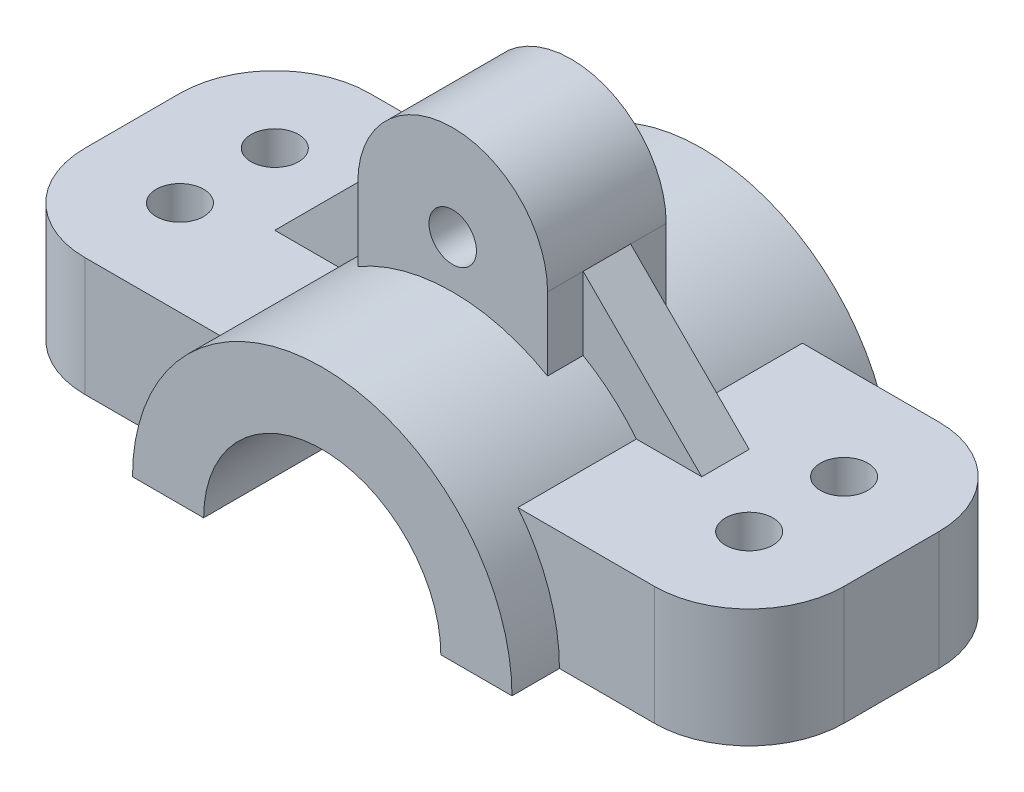
SolidWorks part; units mm, degrees
ref_plane "Front Plane" through (0, 0, 0) normal (0, 0, 1) x (1, 0, 0)
ref_plane "Top Plane" through (0, 0, 0) normal (0, 1, 0) x (1, 0, 0)
ref_plane "Right Plane" through (0, 0, 0) normal (1, 0, 0) x (0, 0, -1)
sketch "Sketch1" plane through (0, 0, 0) normal (0, 0, 1) x (1, 0, 0)
  line L0 (-40, 0) -> (-25, 0)
  line L1 (25, 0) -> (40, 0)
  arc A0 (25, 0) -> (-25, 0) centre (0, 0) ccw
  arc A1 (40, 0) -> (-40, 0) centre (0, 0) ccw
  dimension "D1" = 50
  dimension "D2" = 80
extrude "Boss-Extrude1" add sketch "Sketch1" along normal mid plane 80
sketch "Sketch2" plane through (0, 0, 0) normal (0, -1, 0) x (1, 0, 0)
  line L0 (0, 40) -> (0, 0) construction
  line L1 (25, 40) -> (-25, 40) construction
  line L2 (0, 0) -> (-88.9874, 0) construction
  line L4 (-80, 30) -> (-10, 30)
  line L5 (-80, 30) -> (-80, -30)
  line L6 (-80, -30) -> (-10, -30)
  line L7 (-10, 30) -> (-10, -30)
  dimension "D1" = 80
  dimension "D2" = 60
  dimension "D3" = 10
extrude "Boss-Extrude2" add sketch "Sketch2" against normal blind 25
fillet "Fillet1" radius 20 2 edges at (-80, 12.5, -30) (-80, 12.5, 30)
hole_wizard "Ø10.0 (10) Diameter Hole1" positions "Sketch3" profile "Sketch4" hole size "Ø10.0" standard "ANSI Metric" end condition through all
sketch "Sketch3" plane through (0, 25, 0) normal (0, 1, 0) x (1, 0, 0)
  point P0 (-60, -10)
  point P3 (-60, 10)
sketch "Sketch4" plane through (-60, 25, 10) normal (1, 0, 0) x (0, 0, 1)
  line L0 (0, 0) -> (0, 25)
  line L1 (0, 25) -> (5, 25)
  line L2 (5, 25) -> (5, 0)
  line L5 (5, 0) -> (0, 0)
  line L11 (0, -6.35) -> (0, 107.95) construction
  dimension "Thru Hole Dia." = 10
  dimension "Thru Hole Depth" = 25
mirror "Mirror1" about plane through (0, 0, 0) normal (1, 0, 0) of "Boss-Extrude2", "Fillet1", "Ø10.0 (10) Diameter Hole1"
other "DeleteFace1" face at (-16.1388, 8.3832, 30) face at (-10, 11.4564, 0) face at (-16.1388, 8.3832, -30) face at (16.1388, 8.3832, 30) face at (10, 11.4564, 0) face at (16.1388, 8.3832, -30) and patch yes
sketch "Sketch5" plane through (0, 0, 0) normal (0, 0, 1) x (1, 0, 0)
  line L0 (-20, 50) -> (-20, 34.641)
  line L1 (20, 50) -> (20, 34.641)
  arc A0 (20, 50) -> (-20, 50) centre (0, 50) ccw
  circle A1 centre (0, 50) radius 5
  arc A2 (40, 0) -> (-40, 0) centre (0, 0) ccw construction
  arc A3 (20, 34.641) -> (-20, 34.641) centre (0, 0) ccw
  dimension "D1" = 10
  dimension "D2" = 40
  dimension "D3" = 50
extrude "Boss-Extrude3" add sketch "Sketch5" along normal mid plane 25.003
sketch "Sketch6" plane through (0, 0, 0) normal (0, 0, 1) x (1, 0, 0)
  line L0 (-45, 25) -> (-20, 50)
  line L1 (-31.225, 25) -> (-60, 25) construction
  dimension "D1" = 45
  dimension "D2" = 50
rib "Rib1" sketch "Sketch6" sketch "Sketch6" thickness 10 extrusion direction parallel to sketch draft on no parameters "D1"=10
mirror "Mirror2" about plane through (0, 0, 0) normal (1, 0, 0) of "Rib1"
